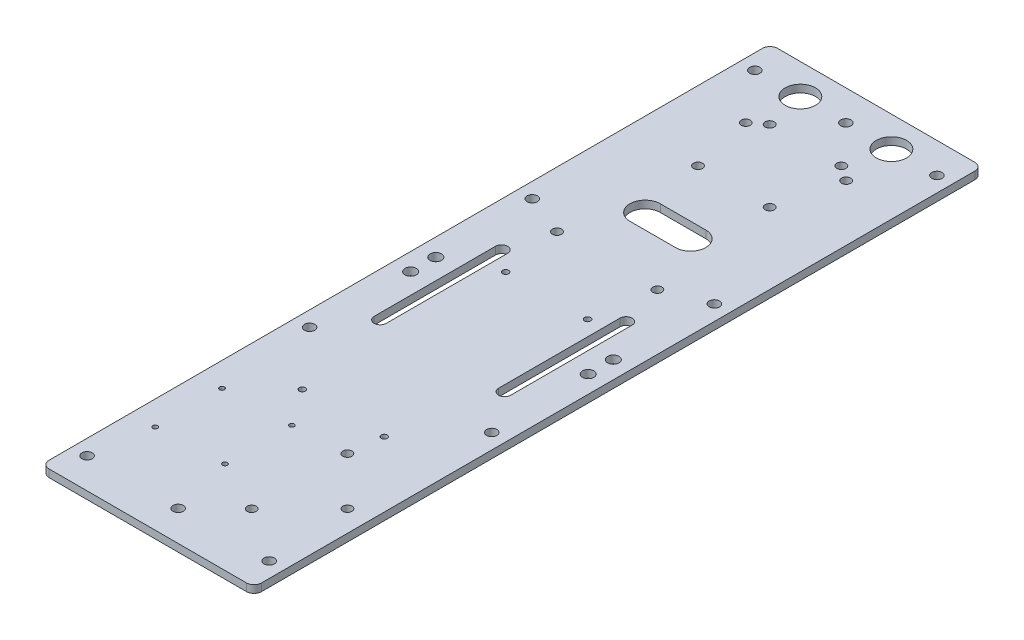
SolidWorks part; units mm, degrees
ref_plane "Front Plane" through (0, 0, 0) normal (0, 0, 1) x (1, 0, 0)
ref_plane "Top Plane" through (0, 0, 0) normal (0, 1, 0) x (1, 0, 0)
ref_plane "Right Plane" through (0, 0, 0) normal (1, 0, 0) x (0, 0, -1)
sketch "Sketch2" plane through (0, 0, 0) normal (0, 1, 0) x (1, 0, 0)
  line L0 (-44.45, 0) -> (44.45, 0) construction
  line L1 (-41.275, 152.4) -> (41.275, 152.4)
  line L2 (-44.45, 149.225) -> (-44.45, -149.225)
  line L3 (-41.275, -152.4) -> (41.275, -152.4)
  line L4 (44.45, 149.225) -> (44.45, -149.225)
  line L5 (0, 152.4) -> (0, -152.4) construction
  arc A0 (-44.45, -149.225) -> (-41.275, -152.4) centre (-41.275, -149.225) ccw
  arc A1 (41.275, -152.4) -> (44.45, -149.225) centre (41.275, -149.225) ccw
  arc A2 (41.275, 152.4) -> (44.45, 149.225) centre (41.275, 149.225) cw
  arc A3 (-41.275, 152.4) -> (-44.45, 149.225) centre (-41.275, 149.225) ccw
  point P8 (0, 0)
  point P13 (-44.45, -152.4)
  point P16 (44.45, -152.4)
  point P21 (-44.45, 152.4)
  dimension "D3" = 3.175
  dimension "D1" = 304.8
  dimension "D2" = 88.9
extrude "Plate Thickness" add sketch "Sketch2" along normal blind 3.175 contours L2 A0 L3 A1 L4 A2 L1 A3
sketch "Sketch3" plane through (0, 3.175, 0) normal (0, 1, 0) x (1, 0, 0)
  line L0 (-44.45, 149.225) -> (-44.45, -149.225) construction
  line L1 (-41.275, 152.4) -> (41.275, 152.4) construction
  line L4 (0, 152.4) -> (0, -152.4) construction
  line L5 (-41.275, -152.4) -> (41.275, -152.4) construction
  line L6 (-41.275, -152.4) -> (41.275, -152.4) construction
  circle A0 centre (-38.1, 139.7) radius 2.159
  circle A1 centre (-38.1, 46.5667) radius 2.159
  circle A2 centre (-38.1, -46.5667) radius 2.159
  circle A3 centre (-38.1, -139.7) radius 2.159
  circle A4 centre (38.1, -139.7) radius 2.159
  circle A5 centre (38.1, -46.5667) radius 2.159
  circle A6 centre (38.1, 46.5667) radius 2.159
  circle A7 centre (38.1, 139.7) radius 2.159
  circle A8 centre (0, 139.7) radius 2.159
  circle A9 centre (0, -139.7) radius 2.159
  dimension "D1" = 4.318
  dimension "D4" = 4.318
  dimension "D2" = 6.35
  dimension "D3" = 12.7
  dimension "D5" = 12.7
  dimension "D6" = 12.7
  dimension "D7" = 93.1333
  dimension "D8" = 93.1333
extrude "Mounting holes" cut sketch "Sketch3" against normal through all
sketch "Sketch4" plane through (0, 3.175, 0) normal (0, 1, 0) x (1, 0, 0)
  line L0 (-21.0058, 39.8143) -> (21.0058, 39.8143) construction
  line L1 (0, 0) -> (0, 139.7) construction
  circle A0 centre (-21.0058, 118.8083) radius 1.905
  circle A1 centre (-21.0058, 39.8143) radius 1.905
  circle A2 centre (21.0058, 39.8143) radius 1.905
  circle A3 centre (21.0058, 118.8083) radius 1.905
  point P13 (0, 39.8143)
  point P17 (0, 69.85)
  point P18 (0, 69.85)
  dimension "D1" = 3.81
  dimension "D2" = 78.994
  dimension "D3" = 42.0116
extrude "Jetson Holes (w/o mount)" cut sketch "Sketch4" against normal through all
sketch "Sketch5" plane through (0, 3.175, 0) normal (0, 1, 0) x (1, 0, 0)
  line L0 (-41.275, 152.4) -> (41.275, 152.4) construction
  line L1 (44.45, 149.225) -> (44.45, -149.225) construction
  circle A1 centre (-15.3784, 123.19) radius 1.905
  circle A3 centre (14.619, 123.19) radius 1.905
  circle A4 centre (14.619, 93.1926) radius 1.905
  circle A5 centre (-15.3784, 93.1926) radius 1.905
  dimension "D1" = 3.81
  dimension "D2" = 29.9974
  dimension "D4" = 29.21
  dimension "D5" = 29.831
  dimension "D3" = 29.9974
extrude "PDB holes" cut sketch "Sketch5" against normal through all
sketch "Sketch6" plane through (0, 3.175, 0) normal (0, 1, 0) x (1, 0, 0)
  line L0 (-41.275, -152.4) -> (41.275, -152.4) construction
  line L1 (44.45, 149.225) -> (44.45, -149.225) construction
  circle A6 centre (35.56, -104.394) radius 1.905
  circle A7 centre (15.56, -84.46) radius 1.905
  circle A8 centre (15.56, -124.46) radius 1.905
  dimension "D1" = 27.94
  dimension "D5" = 3.81
  dimension "D2" = 8.89
  dimension "D6" = 40
  dimension "D7" = 20
  dimension "D8" = 20.066
sketch "Sketch7" plane through (0, 3.175, 0) normal (0, 1, 0) x (1, 0, 0)
  line L0 (0, 152.4) -> (0, -152.4) construction
  line L1 (-41.275, 152.4) -> (41.275, 152.4) construction
  line L2 (-41.275, -152.4) -> (41.275, -152.4) construction
  line L3 (17.145, 14.4893) -> (-17.145, 14.4893) construction
  circle A0 centre (-17.145, 14.4893) radius 1.27
  circle A1 centre (-17.145, -70.6007) radius 1.27
  circle A2 centre (17.145, -70.6007) radius 1.27
  circle A3 centre (17.145, 14.4893) radius 1.27
  point P14 (0, 14.4893)
  dimension "D1" = 2.54
  dimension "D2" = 85.09
  dimension "D3" = 34.29
extrude "PixHawk Holes" cut sketch "Sketch7" against normal through all
sketch "Sketch8" plane through (0, 3.175, 0) normal (0, 1, 0) x (1, 0, 0)
  line L0 (0, 152.4) -> (0, -115.5095) construction
  line L1 (-41.275, 152.4) -> (41.275, 152.4) construction
  line L2 (-26.035, 21.6897) -> (-26.035, -29.1103) construction
  line L3 (-23.495, 21.6897) -> (-23.495, -29.1103)
  line L4 (-28.575, 21.6897) -> (-28.575, -29.1103)
  line L5 (26.035, 21.6897) -> (26.035, -29.1103) construction
  line L6 (23.495, 21.6897) -> (23.495, -29.1103)
  line L7 (28.575, 21.6897) -> (28.575, -29.1103)
  arc A0 (-23.495, 21.6897) -> (-28.575, 21.6897) centre (-26.035, 21.6897) ccw
  arc A1 (-28.575, -29.1103) -> (-23.495, -29.1103) centre (-26.035, -29.1103) ccw
  arc A2 (23.495, 21.6897) -> (28.575, 21.6897) centre (26.035, 21.6897) cw
  arc A3 (28.575, -29.1103) -> (23.495, -29.1103) centre (26.035, -29.1103) cw
  point P7 (-26.035, -3.7103)
  point P14 (26.035, -3.7103)
  dimension "D1" = 50.8
  dimension "D2" = 5.08
  dimension "D3" = 26.035
extrude "Battery Holes" cut sketch "Sketch8" against normal through all
sketch "Sketch9" [suppressed] plane through (0, 3.175, 0) normal (0, 1, 0) x (1, 0, 0)
  line L0 (44.45, 149.225) -> (44.45, -149.225) construction
  line L1 (-41.275, -152.4) -> (41.275, -152.4) construction
  circle A0 centre (6.8334, -85.3) radius 2
  circle A1 centre (34.3334, -85.3) radius 2
  circle A2 centre (34.3334, -114.3) radius 2
  circle A3 centre (6.8334, -114.3) radius 2
  dimension "D1" = 4
  dimension "D3" = 10.1166
  dimension "D5" = 38.1
  dimension "D2" = 27.5
  dimension "D4" = 29
sketch "Sketch10" plane through (0, 3.175, 0) normal (0, 1, 0) x (1, 0, 0)
  line L0 (-44.45, 149.225) -> (-44.45, -149.225) construction
  circle A0 centre (-34.3155, -87.0086) radius 1
  circle A1 centre (-34.29, -115.0086) radius 1
  circle A2 centre (-6.3166, -85.7891) radius 1
  circle A3 centre (-6.3166, -113.7891) radius 1
  dimension "D1" = 2
  dimension "D2" = 28
  dimension "D3" = 28
  dimension "D4" = 28
  dimension "D5" = 10.16
extrude "Ventral Camera holes" cut sketch "Sketch10" against normal up to next
sketch "Sketch12" plane through (0, 3.175, 0) normal (0, 1, 0) x (1, 0, 0)
  line L0 (-41.275, 152.4) -> (41.275, 152.4) construction
  circle A0 centre (-19.05, 139.7) radius 6.35
  circle A1 centre (19.05, 139.7) radius 6.35
  circle A2 centre (-38.1, 139.7) radius 2.159 construction
  dimension "D1" = 19.05
  dimension "D3" = 12.7
  dimension "D2" = 38.1
  dimension "D4" = 12.7
extrude "Wifi antenna holes" cut sketch "Sketch12" against normal through all
extrude "TeraRanger Holes" cut sketch "Sketch6" against normal through all
sketch "Sketch14" plane through (0, 3.175, 0) normal (0, 1, 0) x (1, 0, 0)
  line L0 (0, 0) -> (106.8092, 0) construction
  line L1 (106.8092, 0) -> (-134.4112, 0) construction
  line L2 (0, 0) -> (0, -162.7051) construction
  circle A0 centre (-37.138, 5.2462) radius 2.3812
  circle A1 centre (-37.138, -5.2462) radius 2.3812
  circle A2 centre (37.138, -5.2462) radius 2.3812
  circle A3 centre (37.138, 5.2462) radius 2.3812
  dimension "D1" = 10.4925
  dimension "D2" = 4.7625
extrude "Sonarholes" cut sketch "Sketch14" against normal through all
sketch "Sketch15" plane through (0, 0, 0) normal (0, -1, 0) x (-1, 0, 0)
  line L0 (-9.525, 65.2143) -> (9.525, 65.2143) construction
  line L1 (-9.525, 71.5643) -> (9.525, 71.5643)
  line L2 (-9.525, 58.8643) -> (9.525, 58.8643)
  line L4 (41.275, 152.4) -> (-41.275, 152.4) construction
  arc A0 (-9.525, 71.5643) -> (-9.525, 58.8643) centre (-9.525, 65.2143) ccw
  arc A1 (9.525, 58.8643) -> (9.525, 71.5643) centre (9.525, 65.2143) ccw
  circle A3 centre (-21.0058, 39.8143) radius 1.905 construction
  point P2 (0, 65.2143)
  point P10 (0, 152.4)
  dimension "D1" = 25.4
  dimension "D2" = 19.05
  dimension "D3" = 12.7
extrude "Cut-Extrude1" cut sketch "Sketch15" against normal through all
